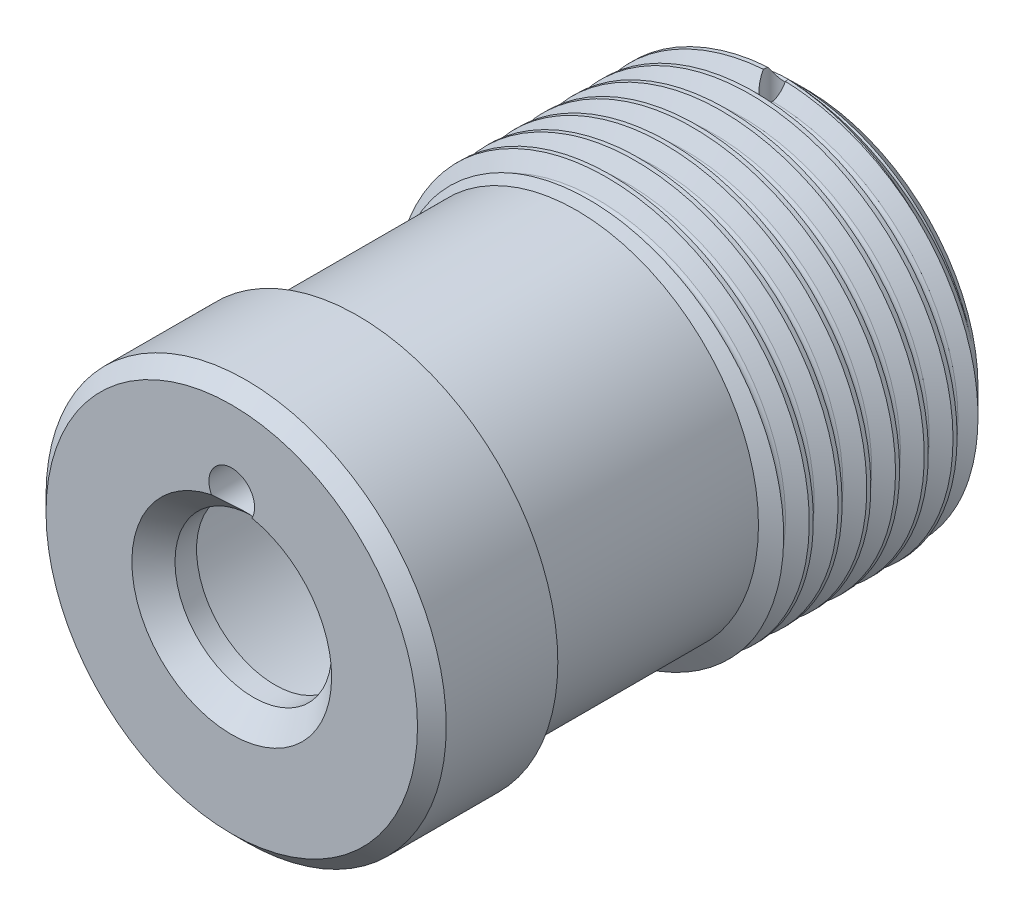
SolidWorks part; units mm, degrees
material "AISI 4130 Steel, normalized at 870C"
ref_plane "Front Plane" through (0, 0, 0) normal (0, 0, 1) x (1, 0, 0)
ref_plane "Top Plane" through (0, 0, 0) normal (0, 1, 0) x (1, 0, 0)
ref_plane "Right Plane" through (0, 0, 0) normal (1, 0, 0) x (0, 0, -1)
sketch "Sketch1" plane through (0, 0, 0) normal (1, 0, 0) x (0, 0, -1)
  line L0 (-46.2567, 0) -> (176.137, 0) construction
  line L1 (0, 19.3) -> (0, 27.85)
  line L3 (80, 25.3) -> (80, 22.15)
  line L6 (0, 27.85) -> (80, 27.85)
  line L7 (80, 27.85) -> (80, 25.3)
  line L8 (6, 17.15) -> (6, 10.9)
  line L9 (6, 10.9) -> (0, 10.9)
  line L10 (0, 10.9) -> (0, 19.3)
  line L12 (11, 22.15) -> (80, 22.15)
  arc A0 (11, 22.15) -> (6, 17.15) centre (11, 17.15) ccw
  dimension "D2" = 5
  dimension "D3" = 80
  dimension "D5" = 55.7
  dimension "D6" = 21.8
  dimension "D8" = 6
  dimension "D11" = 5.7
  dimension "D14" = 44.3
revolve "Revolve1" add sketch "Sketch1" angle 360 about L0
chamfer "Chamfer1" distance 4 angle 45 1 edges at (27.85, 0, -80)
sketch "Sketch2" plane through (0, 0, -80) normal (0, 0, -1) x (-1, 0, 0)
  circle A0 centre (0, 0) radius 28
curve "Helix/Spiral1" pitch 4 height 34.4 radius 28 centre (0, 0, -80) axis (0, 0, 1) start towards (0, 1, 0)
sketch "Sketch3" plane through (0, 0, 0) normal (1, 0, 0) x (0, 0, -1)
  line L0 (83.6021, 28) -> (82.3011, 25.7465)
  line L1 (81.3011, 25.7465) -> (80, 28)
  line L2 (81.8011, 24.8804) -> (81.8011, 29.4651) construction
  line L3 (80, 28) -> (79.7113, 28.5)
  line L4 (79.7113, 28.5) -> (83.8908, 28.5)
  line L5 (83.8908, 28.5) -> (83.6021, 28)
  line L6 (81.3011, 25.7465) -> (82.3011, 25.7465) construction
  line L7 (80, 28) -> (83.6021, 28) construction
  line L8 (0, 0) -> (95.4072, 0) construction
  line L9 (80.8011, 26.6125) -> (82.8011, 26.6125) construction
  arc A0 (81.3011, 25.7465) -> (82.3011, 25.7465) centre (81.8011, 26.0351) ccw
  spline S1 degree 3 poles (80, 28) (79.9431, 28) (79.8288, 27.3214) (79.6577, 24.3408) (79.4866, 19.6117) (79.3154, 13.4737) (79.1443, 6.3678) (78.9731, -1.1956) (78.802, -8.673) (78.6308, -15.5274) (78.4597, -21.2664) (78.2886, -25.4777) (78.1174, -27.8587) (77.9463, -28.2384) (77.7751, -26.5896) (77.604, -23.0307) (77.4328, -17.8173) (77.2617, -11.324) (77.0905, -4.0172) (76.9194, 3.5782) (76.7483, 10.9166) (76.5771, 17.4707) (76.406, 22.7698) (76.2348, 26.4331) (76.0637, 28.1976) (75.8925, 27.9365) (75.7214, 25.6685) (75.5502, 21.5566) (75.3791, 15.8961) (75.208, 9.0936) (75.0368, 1.638) (74.8657, -5.9354) (74.6945, -13.0824) (74.5234, -19.2895) (74.3522, -24.111) (74.1811, -27.2004) (74.01, -28.3358) (73.8388, -27.4357) (73.6677, -24.5647) (73.4965, -19.929) (73.3254, -13.8617) (73.1542, -6.7986) (72.9831, 0.7529) (72.8119, 8.2503) (72.6408, 15.155) (72.4697, 20.9711) (72.2985, 25.2806) (72.1274, 27.7741) (71.9562, 28.2723) (71.7851, 26.7396) (71.6139, 23.286) (71.4428, 18.1595) (71.2716, 11.7286) (71.1005, 4.4551) (70.9294, -3.1384) (70.7582, -10.5065) (70.5871, -17.1198) (70.4159, -22.5033) (70.2448, -26.2702) (70.0736, -28.15) (69.9025, -28.0075) (69.7313, -25.8531) (69.5602, -21.8415) (69.3891, -16.2608) (69.2179, -9.512) (69.0468, -2.0799) (68.8756, 5.5016) (68.7045, 12.6879) (68.5333, 18.9627) (68.3622, 23.8753) (68.191, 27.0728) (68.0199, 28.3255) (67.8488, 27.5433) (67.6776, 24.7825) (67.5065, 20.2415) (67.3353, 14.2463) (67.1642, 7.2277) (66.993, -0.3101) (66.8219, -7.8256) (66.6507, -14.7789) (66.4796, -20.6706) (66.3085, -25.0774) (66.1373, -27.6826) (65.9662, -28.2993) (65.795, -26.883) (65.6239, -23.5355) (65.4527, -18.4974) (65.2816, -12.1304) (65.1104, -4.892) (64.9393, 2.6978) (64.7682, 10.0938) (64.597, 16.7647) (64.4259, 22.2313) (64.2547, 26.1009) (64.0836, 28.0954) (63.9124, 28.0717) (63.7413, 26.0313) (63.5701, 22.121) (63.399, 16.6216) (63.2279, 9.9281) (63.0567, 2.5214) (62.8856, -5.0664) (62.7144, -12.2903) (62.5433, -18.6312) (62.3721, -23.6338) (62.201, -26.9386) (62.0299, -28.3082) (61.8587, -27.6442) (61.6876, -24.9943) (61.5164, -20.549) (61.3453, -14.6274) (61.1741, -7.6551) (61.003, -0.1329) (60.8318, 7.3989) (60.6607, 14.3992) (60.4896, 20.3651) (60.3184, 24.868) (60.1473, 27.5845) (59.9761, 28.3194) (59.805, 27.0199) (59.6338, 23.7794) (59.4627, 18.8307) (59.2915, 12.5292) (59.1204, 5.3277) (58.9493, -2.2566) (58.7781, -9.6787) (58.607, -16.4056) (58.4358, -21.9539) (58.2647, -25.9251) (58.0935, -28.034) (57.9224, -28.129) (57.7512, -26.2032) (57.5801, -22.3952) (57.409, -16.9783) (57.2378, -10.3417) (57.0667, -2.9623) (56.8955, 4.63) (56.7244, 11.8897) (56.5532, 18.2952) (56.3821, 23.3865) (56.2109, 26.7977) (56.0398, 28.2839) (55.8687, 27.7383) (55.6975, 25.2) (55.5264, 20.8515) (55.3552, 15.005) (55.1841, 8.0806) (55.0129, 0.5758) (54.8418, -6.9704) (54.6706, -14.0159) (54.4995, -20.0546) (54.3284, -24.6525) (54.1572, -27.4796) (53.9861, -28.3325) (53.8149, -27.1502) (53.6438, -24.0174) (53.4726, -19.1594) (53.3015, -12.9249) (53.1303, -5.762) (52.9592, 1.8148) (52.7881, 9.2613) (52.6169, 16.0424) (52.4458, 21.6712) (52.2746, 25.7431) (52.1035, 27.9657) (51.9323, 28.1794) (51.7612, 26.3687) (51.59, 22.6638) (51.4189, 17.3308) (51.2478, 10.7528) (51.0766, 3.4024) (50.9055, -4.1925) (50.7343, -11.4862) (50.5632, -17.9547) (50.392, -23.1335) (50.2209, -26.6504) (50.0498, -28.2528) (49.8786, -27.8256) (49.7075, -25.3996) (49.5363, -21.1489) (49.3652, -15.3789) (49.194, -8.5042) (49.0229, -1.0185) (48.8517, 6.5403) (48.6806, 13.6293) (48.5095, 19.7392) (48.3383, 24.4311) (48.1672, 27.3679) (47.996, 28.3387) (47.8249, 27.2738) (47.6537, 24.2496) (47.4826, 19.4834) (47.3114, 13.3175) (47.1403, 6.195) (46.9692, -1.3726) (46.798, -8.8415) (46.6269, -15.6753) (46.4557, -21.3831) (46.2846, -25.5547) (46.1134, -27.8908) (45.9423, -28.2224) (45.7712, -26.5298) (45.6569, -24.1229) (45.6, -22.6525) knots 0 0 0 0 0.004975 0.00995 0.014925 0.0199 0.024876 0.029851 0.034826 0.039801 0.044776 0.049751 0.054726 0.059701 0.064677 0.069652 0.074627 0.079602 0.084577 0.089552 0.094527 0.099502 0.104478 0.109453 0.114428 0.119403 0.124378 0.129353 0.134328 0.139303 0.144279 0.149254 0.154229 0.159204 0.164179 0.169154 0.174129 0.179104 0.18408 0.189055 0.19403 0.199005 0.20398 0.208955 0.21393 0.218905 0.223881 0.228856 0.233831 0.238806 0.243781 0.248756 0.253731 0.258706 0.263682 0.268657 0.273632 0.278607 0.283582 0.288557 0.293532 0.298507 0.303483 0.308458 0.313433 0.318408 0.323383 0.328358 0.333333 0.338308 0.343284 0.348259 0.353234 0.358209 0.363184 0.368159 0.373134 0.378109 0.383085 0.38806 0.393035 0.39801 0.402985 0.40796 0.412935 0.41791 0.422886 0.427861 0.432836 0.437811 0.442786 0.447761 0.452736 0.457711 0.462687 0.467662 0.472637 0.477612 0.482587 0.487562 0.492537 0.497512 0.502488 0.507463 0.512438 0.517413 0.522388 0.527363 0.532338 0.537313 0.542289 0.547264 0.552239 0.557214 0.562189 0.567164 0.572139 0.577114 0.58209 0.587065 0.59204 0.597015 0.60199 0.606965 0.61194 0.616915 0.621891 0.626866 0.631841 0.636816 0.641791 0.646766 0.651741 0.656716 0.661692 0.666667 0.671642 0.676617 0.681592 0.686567 0.691542 0.696517 0.701493 0.706468 0.711443 0.716418 0.721393 0.726368 0.731343 0.736318 0.741294 0.746269 0.751244 0.756219 0.761194 0.766169 0.771144 0.776119 0.781095 0.78607 0.791045 0.79602 0.800995 0.80597 0.810945 0.81592 0.820896 0.825871 0.830846 0.835821 0.840796 0.845771 0.850746 0.855721 0.860697 0.865672 0.870647 0.875622 0.880597 0.885572 0.890547 0.895522 0.900498 0.905473 0.910448 0.915423 0.920398 0.925373 0.930348 0.935323 0.940299 0.945274 0.950249 0.955224 0.960199 0.965174 0.970149 0.975124 0.9801 0.985075 0.99005 0.995025 1 1 1 1 construction
  dimension "D1" = 30
  dimension "D2" = 30
  dimension "D3" = 1
  dimension "D4" = 2
  dimension "D5" = 26.6125
  dimension "D6" = 0.5
sweep "Cut-Sweep1" cut profiles "Sketch3" path "Helix/Spiral1" align with end faces yes
chamfer "Chamfer2" distance 2 angle 45 1 edges at (27.85, 0, 0)
sketch "Sketch4" plane through (0, 0, 0) normal (0, 1, 0) x (1, 0, 0)
  line L0 (22.15, 80) -> (-22.15, 80) construction
  circle A0 centre (0, 75.5) radius 1.5
  dimension "D1" = 3
  dimension "D2" = 4.5
extrude "Cut-Extrude1" cut sketch "Sketch4" against normal through all and the other way through all
sketch "Sketch5" plane through (0, 0, 0) normal (1, 0, 0) x (0, 0, -1)
  line L0 (0, 0) -> (92.3768, 0) construction
  line L1 (48, 25.3) -> (19, 25.3)
  line L2 (19, 25.3) -> (14.6603, 32.8166)
  line L3 (14.6603, 32.8166) -> (52.3397, 32.8166)
  line L4 (52.3397, 32.8166) -> (48, 25.3)
  line L6 (80, -23.85) -> (80, 23.85) construction
  dimension "D1" = 60
  dimension "D2" = 29
  dimension "D3" = 32
  dimension "D4" = 60
  dimension "D5" = 50.6
revolve "Cut-Revolve1" cut sketch "Sketch5" angle 360 about L0
chamfer "Chamfer3" distance 3 angle 45 1 edges at (10.9, 0, 0)
sketch "Sketch6" plane through (0, 0, 0) normal (0, 0, 1) x (1, 0, 0)
  line L0 (0, 10.9) -> (31.5175, 10.9) construction
  line L1 (0, 11.9) -> (31.5175, 11.9) construction
  circle A0 centre (0, 15.075) radius 3.175
  circle A1 centre (0, 0) radius 10.9 construction
  dimension "D1" = 6.35
  dimension "D2" = 1
  dimension "D3" = 15.075
extrude "Cut-Extrude2" cut sketch "Sketch6" against normal through all
